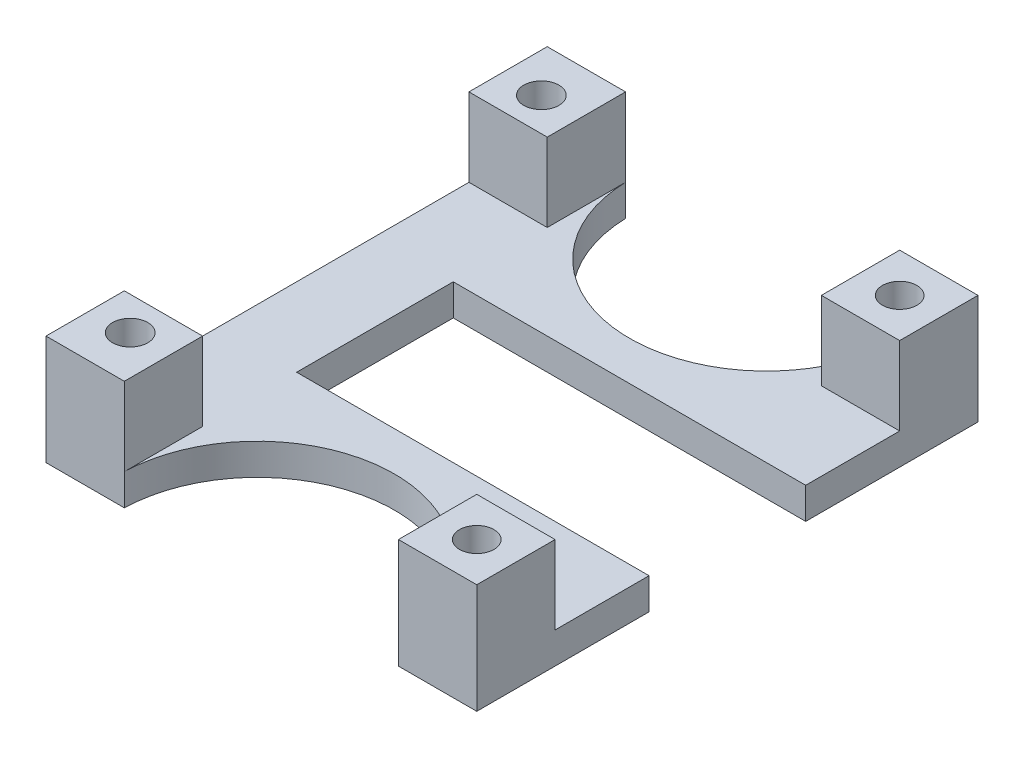
SolidWorks part; units mm, degrees
ref_plane "Front Plane" through (0, 0, 0) normal (0, 0, 1) x (1, 0, 0)
ref_plane "Top Plane" through (0, 0, 0) normal (0, 1, 0) x (1, 0, 0)
ref_plane "Right Plane" through (0, 0, 0) normal (1, 0, 0) x (0, 0, -1)
sketch "Sketch1" plane through (0, 0, 0) normal (0, 1, 0) x (1, 0, 0)
  line L0 (10, 10) -> (10, -10)
  line L2 (0, -20) -> (0, 20)
  line L4 (55, -20) -> (55, 20) construction
  line L5 (10, -10) -> (45, -10)
  line L6 (45, -10) -> (45, 10) construction
  line L7 (45, 10) -> (10, 10)
  line L8 (45, 10) -> (55, 10)
  line L11 (55, 10) -> (55, 20)
  line L13 (27.5, -20) -> (27.5, -10) construction
  line L14 (27.5, 10) -> (27.5, 20) construction
  line L16 (45, -10) -> (55, -10)
  line L17 (55, -20) -> (55, -10)
  line L18 (55, -20) -> (55, -32)
  line L19 (55, -32) -> (45, -32)
  line L21 (55, 20) -> (55, 32)
  line L22 (55, 32) -> (45, 32)
  line L24 (0, -20) -> (0, -32)
  line L27 (0, 20) -> (0, 32)
  line L30 (-55, 0) -> (55, 0) construction
  line L31 (0, 0) -> (55, 0) construction
  line L32 (10, -32) -> (0, -32)
  line L34 (10, 32) -> (0, 32)
  arc A26 (45, -32) -> (10, -32) centre (27.5, -32.5074) ccw
  arc A27 (45, 32) -> (10, 32) centre (27.5, 32.5074) cw
  circle A46 centre (50, 27) radius 2.2
  circle A47 centre (50, -27) radius 2.2
  circle A49 centre (5, -26.25) radius 2.2479 construction
  circle A50 centre (5, -26.25) radius 2.2479
  circle A51 centre (5, 26.25) radius 2.2479 construction
  circle A52 centre (5, 26.25) radius 2.2479
  point P17 (45, 32)
  point P20 (11.3465, 32)
  point P21 (10, 32)
  point P28 (25.6771, 20)
  point P30 (27.5, -15)
  point P35 (27.5, 15)
  point P36 (27.5, -10)
  point P39 (0, 0)
  dimension "D18" = 4.4
  dimension "D1" = 40
  dimension "D2" = 55
  dimension "D24" = 10
  dimension "D13" = 5
  dimension "D16" = 5
  dimension "D7" = 10
  dimension "D9" = 5
  dimension "D14" = 5
  dimension "D4" = 20
  dimension "D5" = 10
  dimension "D3" = 10
  dimension "D6" = 35
  dimension "D8" = 12
  dimension "D10" = 10
extrude "Extrude-Body" add sketch "Sketch1" along normal blind 4 contours L4 L2 A47 A46 L7 L6 L5 L0 | L19 L18 A47 | L22 L21 A46 | L27 | L24 region at (9.1561, 0, 0)
sketch "Sketch5" plane through (0, 4, 0) normal (0, 1, 0) x (1, 0, 0)
  line L6 (10, -32) -> (0, -32) construction
  line L9 (45, -22) -> (55, -22)
  line L21 (55, -22) -> (55, -32)
  line L23 (0, -32) -> (0, 32) construction
  line L34 (10, 32) -> (0, 32) construction
  line L36 (55, -32) -> (45, -32)
  line L37 (45, -32) -> (45, -22)
  line L38 (55, 22) -> (55, 32)
  line L39 (55, 32) -> (45, 32)
  line L41 (45, 32) -> (45, 22)
  line L42 (45, 22) -> (55, 22)
  line L43 (10, 22) -> (10, 32)
  line L44 (10, 32) -> (0, 32)
  line L46 (0, 32) -> (0, 22)
  line L47 (0, -32) -> (0, 32) construction
  line L48 (0, 22) -> (10, 22)
  line L49 (10, -22) -> (0, -22)
  line L50 (0, -22) -> (0, -32)
  line L51 (0, -32) -> (10, -32)
  line L52 (10, -32) -> (10, -22)
  circle A0 centre (50, 27) radius 2.2
  circle A3 centre (50, -27) radius 2.2
  circle A11 centre (50, 27) radius 2.2 construction
  circle A12 centre (50, -27) radius 2.2 construction
  circle A13 centre (5, 26.25) radius 2.2479 construction
  circle A14 centre (5, 26.25) radius 2.2479
  circle A15 centre (5, -26.25) radius 2.2479 construction
  circle A16 centre (5, -26.25) radius 2.2479
  point P18 (0, 0)
  point P19 (9.8604, -23.2987)
  point P22 (0, 0)
  point P23 (0, 0)
  point P24 (10, 31.5963)
  point P28 (0, 0)
  point P44 (0, 0)
  dimension "D1" = 10
  dimension "D2" = 10
  dimension "D3" = 10
  dimension "D4" = 10
  dimension "D5" = 10
  dimension "D6" = 10
  dimension "D8" = 10
extrude "Extrude-Legs" add sketch "Sketch5" along normal blind 10
equation "\"boltdiameter\"=4.4"
equation "\"D18@Sketch1\"=\"boltdiameter\""
equation "\"boltfacediameter\"=7"
equation "\"insetNutFlat\"=8.4"
equation "\"screwInset\"=8.43"
equation "\"slotLength\"=80"
